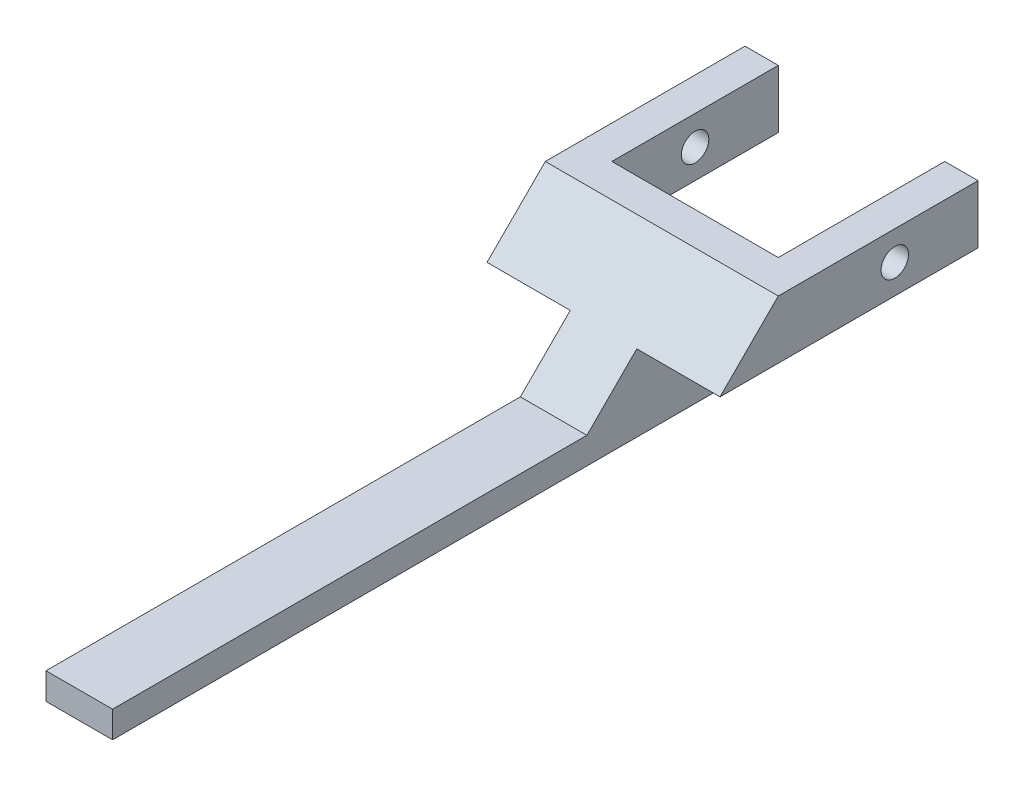
SolidWorks part; units mm, degrees
ref_plane "Front Plane" through (0, 0, 0) normal (0, 0, 1) x (1, 0, 0)
ref_plane "Top Plane" through (0, 0, 0) normal (0, 1, 0) x (1, 0, 0)
ref_plane "Right Plane" through (0, 0, 0) normal (1, 0, 0) x (0, 0, -1)
sketch "Sketch1" plane through (0, 0, 0) normal (0, 0, 1) x (1, 0, 0)
  line L1 (0, 0) -> (20, 0)
  line L2 (0, 0) -> (0, 7)
  line L3 (0, 7) -> (20, 7)
  line L4 (20, 0) -> (20, 7)
  line L5 (0, 7) -> (-4, 7)
  line L6 (0, 7) -> (0, 0)
  line L7 (0, 0) -> (-4, 0)
  line L8 (-4, 7) -> (-4, 0)
  line L9 (20, 7) -> (24, 7)
  line L10 (20, 7) -> (20, 0)
  line L11 (20, 0) -> (24, 0)
  line L12 (24, 7) -> (24, 0)
  dimension "D1" = 20
  dimension "D2" = 4
  dimension "D3" = 4
  dimension "D4" = 7
extrude "Boss-Extrude1" add sketch "Sketch1" along normal blind 24 contours L5 L8 L7 L2 | L12 L9 L4 L11 region at (-2, 3.5, 0) region at (22, 3.5, 0)
extrude "Boss-Extrude2" add sketch "Sketch1<3>" along normal blind 4 from offset 20 contours L1 L4 L3 L2 region at (10, 3.5, 0)
sketch "Sketch1<3>" plane through (0, 0, 0) normal (0, 0, 1) x (1, 0, 0) same geometry as "Sketch1"
sketch "Sketch2" plane through (0, 0, 24) normal (0, 0, 1) x (1, 0, 0)
  line L0 (10, 7) -> (10, -6) construction
  line L1 (24, 7) -> (-4, 7) construction
  line L3 (6, -6) -> (14, -6)
  line L4 (6, -6) -> (6, -8.1934)
  line L5 (6, -8.1934) -> (14, -8.1934)
  line L6 (14, -6) -> (14, -8.1934)
  dimension "D1" = 13
  dimension "D2" = 4
  dimension "D3" = 4
extrude "Boss-Extrude3" add sketch "Sketch2" along normal blind 70 separate body
sketch "Sketch3" plane through (0, 0, 24) normal (0, 0, -1) x (-1, 0, 0)
  line L0 (-6, -8.1934) -> (-6, 0)
  line L1 (-14, -8.1934) -> (-6, -8.1934)
  line L2 (-14, -8.1934) -> (-14, 0)
  line L5 (0, 0) -> (-20, 0) construction
  line L6 (-6, 0) -> (-14, 0)
extrude "Boss-Extrude4" add sketch "Sketch3" along normal up to surface (4 mm away) up to face at (10, 3.5, 20)
sketch "Sketch4" plane through (24, 0, 0) normal (1, 0, 0) x (0, 0, -1)
  line L0 (0, 7) -> (-10, 7) construction
  line L1 (-24, 7) -> (0, 7) construction
  line L2 (-10, 7) -> (-10, 0) construction
  line L3 (-24, 0) -> (0, 0) construction
  circle A0 centre (-10, 3.5) radius 1.65
  dimension "D2" = 3.3
  dimension "D1" = 10
extrude "Cut-Extrude1" cut sketch "Sketch4" against normal up to surface (28 mm away) up to face at (-4, 3.5, 12)
chamfer "Chamfer1" distance 13 angle 45 1 edges at (10, -6, 24)
sketch "Sketch5" plane through (0, -8.1934, 0) normal (0, -1, 0) x (1, 0, 0)
  line L1 (6, 94) -> (14, 94)
  line L2 (6, 94) -> (6, 20)
  line L3 (6, 20) -> (14, 20)
  line L4 (14, 94) -> (14, 20)
extrude "Boss-Extrude5" add sketch "Sketch5" along normal blind 1
